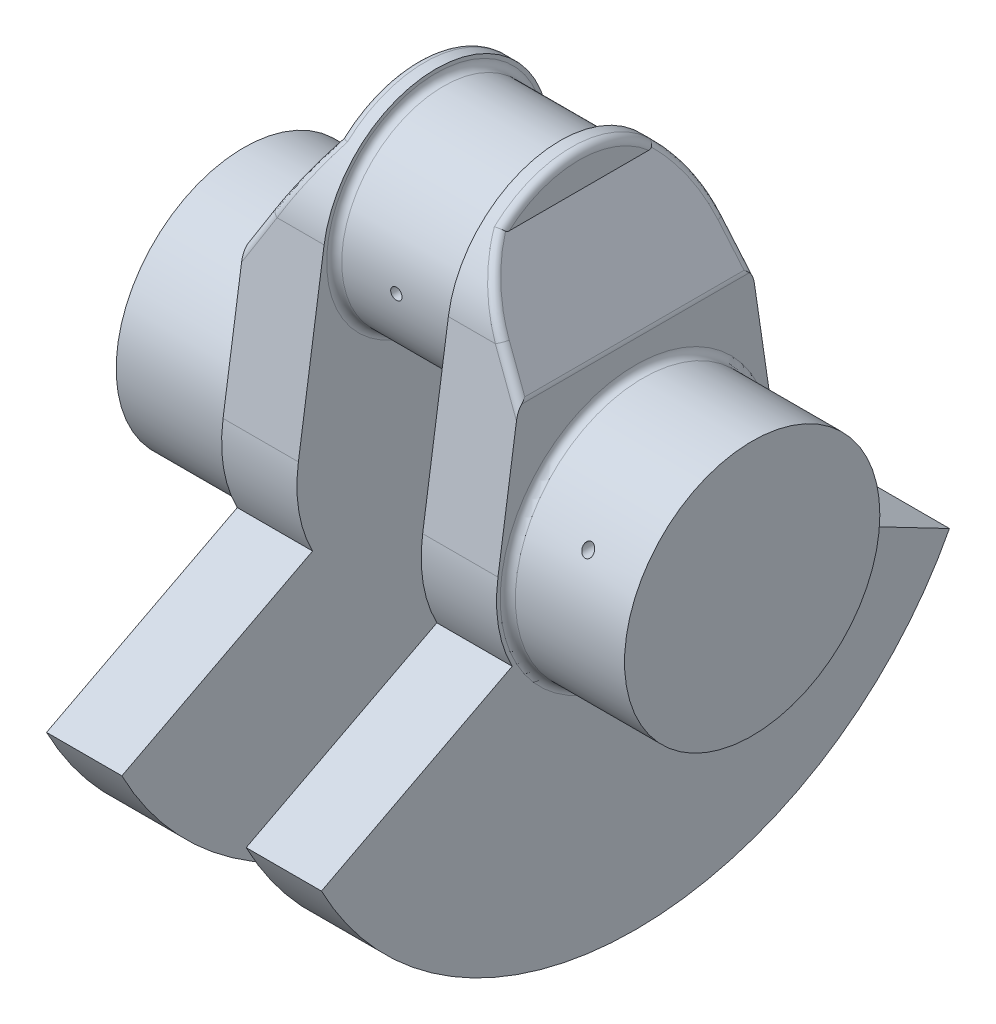
SolidWorks part; units mm, degrees
ref_plane "Спереди" through (0, 0, 0) normal (0, 0, 1) x (1, 0, 0)
ref_plane "Сверху" through (0, 0, 0) normal (0, 1, 0) x (1, 0, 0)
ref_plane "Справа" through (0, 0, 0) normal (1, 0, 0) x (0, 0, -1)
sketch "Эскиз3" plane through (0, 0, 0) normal (1, 0, 0) x (0, 0, -1)
  circle A0 centre (0, 0) radius 33.9
  dimension "D1" = 67.8
extrude "Бобышка-Вытянуть1" add sketch "Эскиз3" along normal blind 31 contours A0
sketch "Эскиз4" plane through (31, 0, 0) normal (1, 0, 0) x (0, 0, -1)
  line L0 (-29.6818, 51.8579) -> (-36.5086, 5.3602)
  line L1 (29.6818, 51.8579) -> (36.5086, 5.3602)
  line L2 (-83.379, -43.4044) -> (0, 0)
  line L3 (0, -47) -> (0, 0)
  line L4 (83.379, -43.4044) -> (0, 0)
  circle A0 centre (0, 0) radius 36.9
  circle A1 centre (0, 47.5) radius 30
  circle A2 centre (0, 0) radius 33.9 construction
  arc A3 (83.379, -43.4044) -> (-83.379, -43.4044) centre (0, 0) cw
  circle M1 centre (0, 0) radius 33.9
  dimension "D1" = 47.5
  dimension "D2" = 60
  dimension "D4" = 94
  dimension "D3" = 3
  dimension "D5" = 117.5
extrude "Бобышка-Вытянуть2" add sketch "Эскиз4" along normal blind 20 contours A1 A0 | A0 A1 M1 | A1 M1 | A1 A0 L1 | A1 A0 M1 | A1 M1 | A1 L0 A0 | A0 | L4 A3 L2 region at (31, 28.8579, 30.213) region at (31, 53.1931, 0) region at (31, 28.8579, -30.213) region at (31, 36.4222, 0) region at (31, 2.6521, -36.3209) region at (31, 25.8071, 0) region at (31, 5.6798, 0)
sketch "Эскиз6" plane through (0, 0, 0) normal (0, 0, 1) x (1, 0, 0)
  line L0 (31, 77.5) -> (46, 77.5)
  line L1 (51, 77.5) -> (31, 77.5) construction
  line L2 (46, 77.5) -> (46, 68.5)
  line L3 (46, 68.5) -> (31, 42.5192)
  line L4 (31, 77.5) -> (31, 51.8579) construction
  line L5 (31, 42.5192) -> (31, 77.5)
  dimension "D1" = 5
  dimension "D2" = 60
  dimension "D3" = 9
extrude "Вырез-Вытянуть1" cut sketch "Эскиз6" against normal through all and the other way through all
fillet "Скругление1" radius 2 6 edges at (31, 42.5192, 0) (33.6958, 47.1886, -30.3673) (41.5742, 60.8343, -26.8737) (33.6958, 47.1886, 30.3673) (41.5742, 60.8343, 26.8737) (46, 77.5, 0)
sketch "Эскиз5" plane through (51, 0, 0) normal (1, 0, 0) x (0, 0, -1)
  circle A1 centre (0, 47.5) radius 27
  dimension "D1" = 54
  dimension "D2" = 47.5
extrude "Бобышка-Вытянуть3" add sketch "Эскиз5" along normal blind 16.5
fillet "Скругление2" radius 2 1 edges at (51, 47.5, -27)
fillet "Скругление3" radius 2 1 edges at (31, 0, -33.9)
ref_axis "Ось1" through (67.5, -102.575, 0) along (0, 1, 0)
mirror "Зеркальное отражение4" about plane through (67.5, 47.5, 0) normal (1, 0, 0) of bodies 103 111
sketch "Эскиз10" plane through (0, 0, 0) normal (0, 0, 1) x (1, 0, 0)
  line L0 (67.5, 74.5) -> (67.5, 20.5)
  line L1 (82, 74.5) -> (53, 74.5) construction
  line L2 (53, 20.5) -> (82, 20.5) construction
  circle A0 centre (67.5, 47.5) radius 1.5
extrude "Вырез-Вытянуть3" cut sketch "Эскиз10" against normal through all both and the other way through all contours A0
ref_axis "Ось8" through (67.5, 47.5, -27) along (0, 0, 1)
ref_plane "Плоскость10" through (37.4431, 64.8534, 0) normal (-0.5, -0.866, 0) x (0, 0, 1)
ref_axis "Ось9" through (42.2817, 62.0598, 32.0212) along (0, 0, -1)
sketch "Эскиз12" plane through (4.8386, -2.7936, 0) normal (-0.866, 0.5, 0) x (0, 0, 1)
  line L0 (-29.1101, 52.8586) -> (29.1101, 52.8586)
  line L1 (29.1101, 52.8586) -> (27.703, 63.9253) construction
  line L2 (-29.1101, 52.8586) -> (29.1101, 52.8586) construction
  line L3 (-32.0212, 74.8862) -> (32.0212, 74.8862) construction
  circle A0 centre (0, 74.8862) radius 1.5
extrude "Вырез-Вытянуть5" cut sketch "Эскиз12" against normal offset from surface (95 mm away) 95 contours A0 region at (42.2817, 62.0598, 0) up to face at (40.1452, 58.3592, 0.0296)
ref_axis "Ось10" through (182.3675, -18.8188, 0) along (-0.866, 0.5, 0)
ref_plane "Плоскость11" through (121, 0, 0) normal (1, 0, 0) x (0, 0, -1)
ref_axis "Ось12" through (121, 16.6118, -32.0212) along (0, 0, 1)
ref_plane "Плоскость13" through (0, 0, 0) normal (0, 0, 1) x (1, 0, 0)
sketch "Эскиз14" plane through (0, 0, 0) normal (0, 0, 1) x (1, 0, 0)
  line L0 (121, -91.7169) -> (121, 91.7169) construction
  line L1 (9.712, 80.8639) -> (65.1742, 48.8428) construction
  circle A0 centre (121, 16.6118) radius 1.5
extrude "Вырез-Вытянуть6" cut sketch "Эскиз14" against normal through all both and the other way through all
